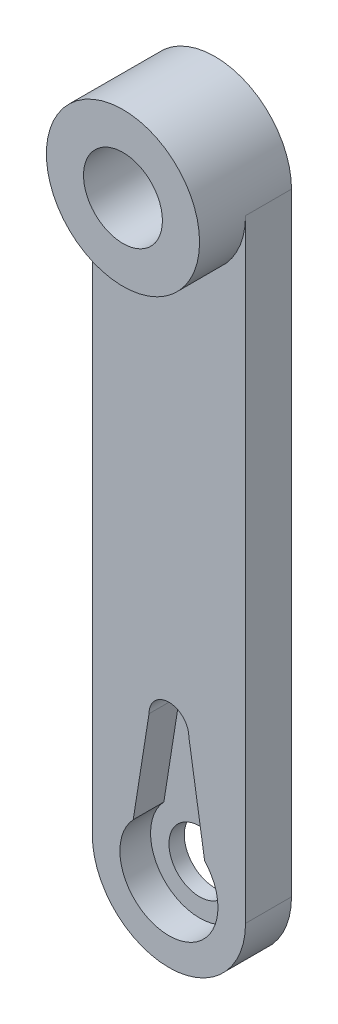
SolidWorks part; units mm, degrees
ref_plane "Спереди" through (0, 0, 0) normal (0, 0, 1) x (1, 0, 0)
ref_plane "Сверху" through (0, 0, 0) normal (0, 1, 0) x (1, 0, 0)
ref_plane "Справа" through (0, 0, 0) normal (1, 0, 0) x (0, 0, -1)
sketch "Эскиз1" plane through (0, 0, 0) normal (0, 0, 1) x (1, 0, 0)
  line L0 (0, 0) -> (0, 80) construction
  line L1 (-10, 0) -> (-10, 80)
  line L2 (10, 80) -> (10, 0)
  circle A0 centre (0, 0) radius 10
  circle A1 centre (0, 80) radius 10
  circle A2 centre (0, 80) radius 5.15
  circle A3 centre (0, 0) radius 4
  dimension "D1" = 20
  dimension "D3" = 10.3
  dimension "D4" = 8
  dimension "D2" = 80
extrude "Бобышка-Вытянуть1" add sketch "Эскиз1" along normal blind 6 contours A0 L0 A1 L1 | L0 A0 L2 A1 | A0 region at (6.8711, 6.8711, 0) region at (-5.1847, 40, 0) region at (5.1847, 40, 0)
extrude "Бобышка-Вытянуть2" add sketch "Эскиз1<3>" along normal blind 12 contours A1 A2 region at (0, 89.7172, 0)
sketch "Эскиз1<3>" plane through (0, 0, 0) normal (0, 0, 1) x (1, 0, 0) same geometry as "Эскиз1"
sketch "Эскиз2" plane through (0, 0, 6) normal (0, 0, 1) x (1, 0, 0)
  line L0 (0, 17.4) -> (0, 0) construction
  line L1 (-2.6, 17.4) -> (-4.6613, 4.3855)
  line L2 (2.6, 17.4) -> (4.6613, 4.3855)
  circle A0 centre (0, 0) radius 6.4
  circle A1 centre (0, 17.4) radius 2.6
  dimension "D1" = 12.8
  dimension "D3" = 5.2
  dimension "D2" = 17.4
  dimension "D4" = 18
extrude "Вырез-Вытянуть1" cut sketch "Эскиз2" against normal blind 4 contours A1 | L0 A1 L1 A0 | A1 L0 A0 L2 | A0 region at (1.9913, 10.3041, 6) region at (-1.9913, 10.3041, 6) region at (-1.7865, 15.6135, 6) region at (2.4672, 5.7087, 6)
